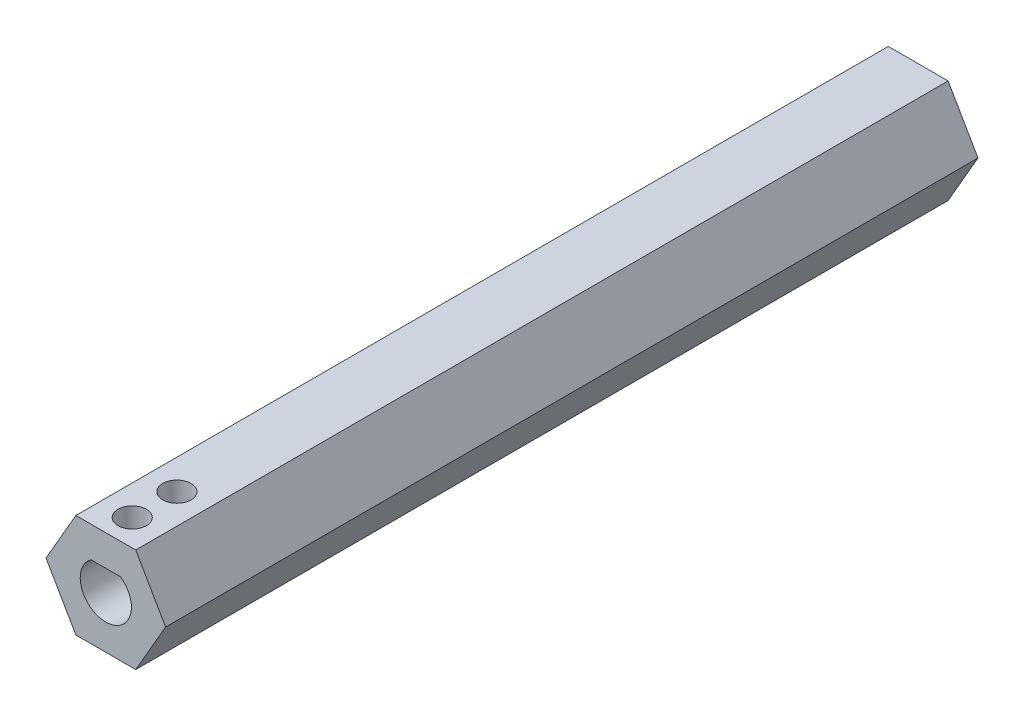
SolidWorks part; units mm, degrees
ref_plane "Alzado" through (0, 0, 0) normal (0, 0, 1) x (1, 0, 0)
ref_plane "Planta" through (0, 0, 0) normal (0, 1, 0) x (1, 0, 0)
ref_plane "Vista lateral" through (0, 0, 0) normal (1, 0, 0) x (0, 0, -1)
sketch "Croquis1" plane through (0, 0, 0) normal (0, 0, 1) x (1, 0, 0)
  line L0 (0, 0) -> (0, 2.5851) construction
  line L1 (7.3617, 0) -> (3.6808, 6.3754)
  line L2 (3.6808, 6.3754) -> (-3.6808, 6.3754)
  line L3 (-3.6808, 6.3754) -> (-7.3617, 0)
  line L4 (-7.3617, 0) -> (-3.6808, -6.3754)
  line L5 (-3.6808, -6.3754) -> (3.6808, -6.3754)
  line L6 (3.6808, -6.3754) -> (7.3617, 0)
  line L7 (-1.8, 2.5851) -> (1.8, 2.5851)
  circle A0 centre (0, 0) radius 6.3754 construction
  arc A1 (-1.8, 2.5851) -> (1.8, 2.5851) centre (0, 0) ccw
  point P1 (0, 0)
  point P10 (0, 0)
  point P14 (0, 2.5851)
  dimension "D2" = 6.3
  dimension "D1" = 12.7508
  dimension "D3" = 3.6
extrude "Saliente-Extruir1" add sketch "Croquis1" along normal blind 100
sketch "Croquis2" plane through (0, 6.3754, 0) normal (0, 1, 0) x (1, 0, 0)
  line L0 (0, -100) -> (0, -96.75) construction
  line L1 (3.6808, -100) -> (-3.6808, -100) construction
  line L2 (0, -96.75) -> (0, -95) construction
  line L3 (0, -95) -> (0, -93) construction
  line L4 (0, -93) -> (0, -91.25) construction
  line L5 (0, -91.25) -> (0, -88) construction
  circle A0 centre (0, -96.75) radius 1.75
  circle A1 centre (0, -91.25) radius 1.75
  point P9 (0, 0)
  point P11 (0, -86.2573)
  dimension "D1" = 3.5
  dimension "D2" = 12
  dimension "D3" = 2
extrude "Cortar-Extruir1" cut sketch "Croquis2" against normal blind 7.5
